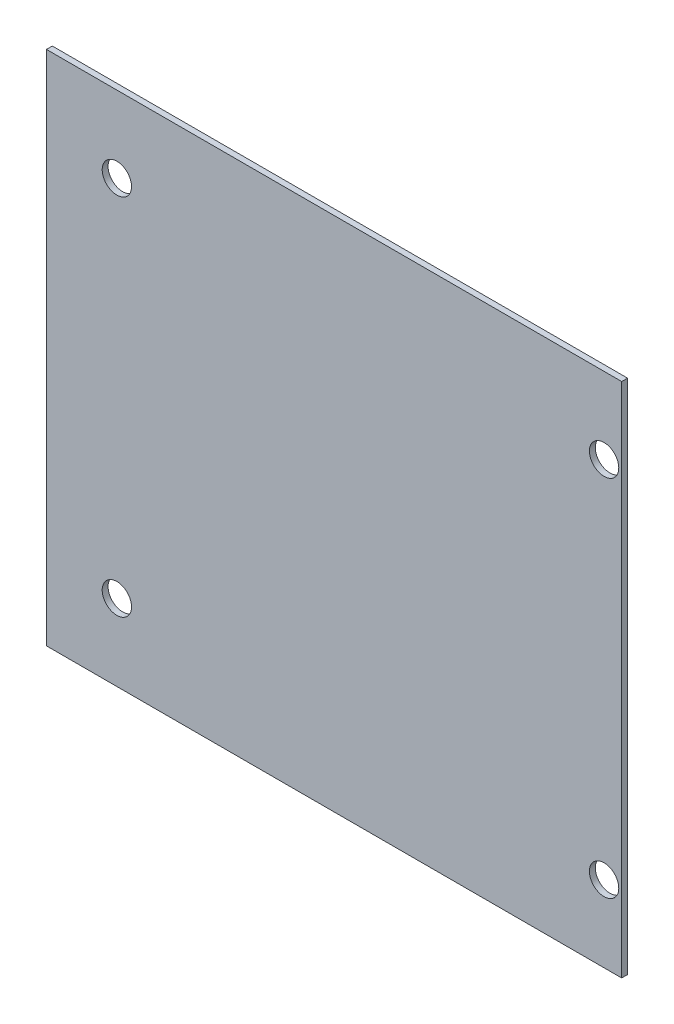
SolidWorks part; units mm, degrees
ref_plane "Front Plane" through (0, 0, 0) normal (0, 0, 1) x (1, 0, 0)
ref_plane "Top Plane" through (0, 0, 0) normal (0, 1, 0) x (1, 0, 0)
ref_plane "Right Plane" through (0, 0, 0) normal (1, 0, 0) x (0, 0, -1)
sketch "Sketch1" plane through (0, 0, 0) normal (0, 0, 1) x (1, 0, 0)
  line L1 (49, -44) -> (-49, -44)
  line L2 (49, -44) -> (49, 44)
  line L3 (49, 44) -> (-49, 44)
  line L4 (-49, -44) -> (-49, 44)
  line L5 (49, -44) -> (-49, 44) construction
  line L6 (49, 44) -> (-49, -44) construction
  line L7 (46, -31) -> (-37, -31)
  line L8 (46, -31) -> (46, 31)
  line L9 (46, 31) -> (-37, 31)
  line L10 (-37, -31) -> (-37, 31)
  line L11 (46, -31) -> (-37, 31) construction
  line L12 (46, 31) -> (-37, -31) construction
  circle A0 centre (-37, 31) radius 2.5
  circle A1 centre (46, 31) radius 2.5
  circle A2 centre (46, -31) radius 2.5
  circle A3 centre (-37, -31) radius 2.5
  point P0 (0, 0)
  point P6 (4.5, 0)
  dimension "D6" = 5
  dimension "D1" = 88
  dimension "D2" = 98
  dimension "D3" = 62
  dimension "D4" = 83
  dimension "D5" = 12
extrude "Boss-Extrude1" add sketch "Sketch1" along normal blind 1 contours L4 L1 L2 L3 A3 L10 A0 L9 A1 L8 A2 L7 | A3 L7 A2 L8 A1 L9 A0 L10 region at (0, -42.6829, 0) region at (4.5, 0, 0)
